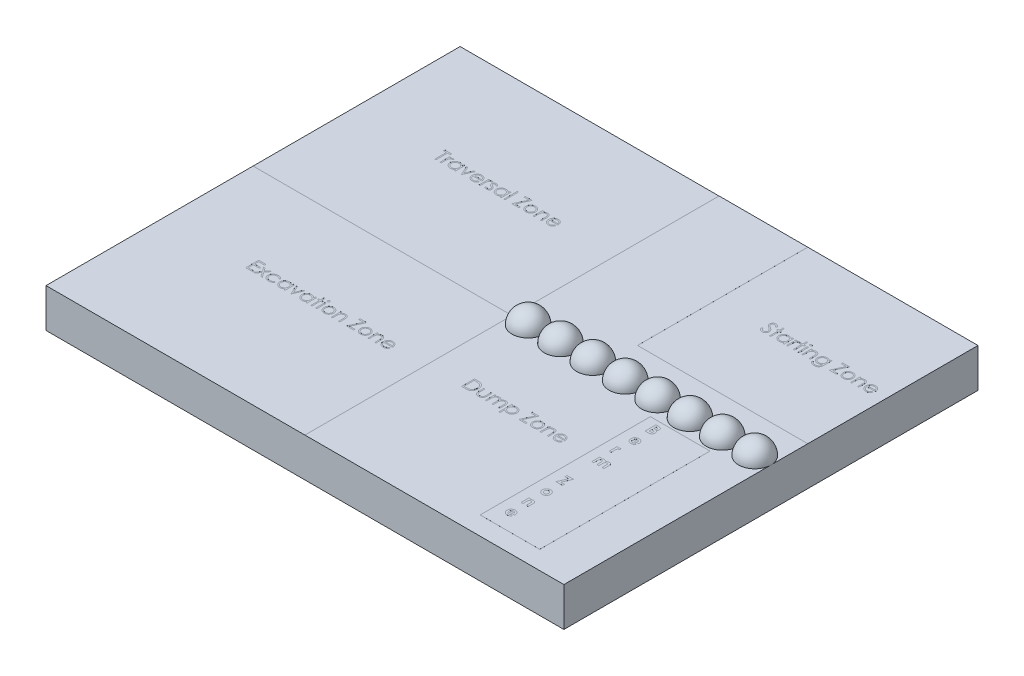
SolidWorks part; units mm, degrees
ref_plane "Front Plane" through (0, 0, 0) normal (0, 0, 1) x (1, 0, 0)
ref_plane "Top Plane" through (0, 0, 0) normal (0, 1, 0) x (1, 0, 0)
ref_plane "Right Plane" through (0, 0, 0) normal (1, 0, 0) x (0, 0, -1)
sketch "Sketch1" plane through (0, 0, 0) normal (0, 1, 0) x (1, 0, 0)
  line L1 (-3042.412, -2432.812) -> (3042.412, -2432.812)
  line L2 (-3042.412, -2432.812) -> (-3042.412, 2432.812)
  line L3 (-3042.412, 2432.812) -> (3042.412, 2432.812)
  line L4 (3042.412, -2432.812) -> (3042.412, 2432.812)
  line L5 (-3042.412, -2432.812) -> (3042.412, 2432.812) construction
  line L6 (-3042.412, 2432.812) -> (3042.412, -2432.812) construction
  point P0 (0, 0)
  dimension "D1" = 4865.624
  dimension "D2" = 6084.824
extrude "Boss-Extrude1" add sketch "Sketch1" along normal blind 457.2
sketch "Sketch2" plane through (0, 457.2, 0) normal (0, 1, 0) x (1, 0, 0)
  line L0 (-3042.412, 0) -> (3042.412, 0)
  line L1 (-3042.412, 2432.812) -> (-3042.412, -2432.812) construction
  line L2 (3042.412, -2432.812) -> (3042.412, 2432.812) construction
  line L3 (0, 2432.812) -> (0, -2432.812)
  line L4 (3042.412, 2432.812) -> (-3042.412, 2432.812) construction
  line L5 (-3042.412, -2432.812) -> (3042.412, -2432.812) construction
  line L7 (-3042.412, -2432.812) -> (3042.412, -2432.812)
  line L8 (-3042.412, -2432.812) -> (-3042.412, 2432.812)
  line L9 (-3042.412, 2432.812) -> (3042.412, 2432.812)
  line L10 (3042.412, -2432.812) -> (3042.412, 2432.812)
  line L11 (-3042.412, -2432.812) -> (3042.412, 2432.812) construction
  line L12 (-3042.412, 2432.812) -> (3042.412, -2432.812) construction
  point P12 (0, 0)
  line M5 (3042.412, -2432.812) -> (3042.412, 2432.812)
  line M6 (3042.412, 2432.812) -> (-3042.412, 2432.812)
  line M7 (-3042.412, 2432.812) -> (-3042.412, -2432.812)
  line M8 (-3042.412, -2432.812) -> (3042.412, -2432.812)
extrude "Cut-Extrude3" cut sketch "Sketch2" against normal blind 0.254 contours L3 L0 M7 M8 region at (-1521.206, 457.2, 1216.406)
extrude "Boss-Extrude2" add sketch "Sketch2<5>" along normal blind 0.254 contours L3 L0 M6 M5 region at (1521.206, 457.2, -1216.406)
sketch "Sketch2<5>" plane through (0, 457.2, 0) normal (0, 1, 0) x (1, 0, 0) same geometry as "Sketch2"
sketch "Sketch4" plane through (0, 457.2, 0) normal (0, 1, 0) x (1, 0, 0)
  line L0 (0, 0) -> (3042.412, 0) construction
  line L1 (0, 0) -> (3042.412, 0) construction
  line L2 (3042.412, 0) -> (3042.412, 2432.812) construction
  line L3 (0, 0) -> (3042.412, 0)
  arc A0 (0, 0) -> (380.3015, 0) centre (190.1508, 0) ccw
  arc A3 (380.3015, 0) -> (760.603, 0) centre (570.4523, 0) ccw
  arc A4 (760.603, 0) -> (1140.9045, 0) centre (950.7538, 0) ccw
  arc A5 (1140.9045, 0) -> (1521.206, 0) centre (1331.0553, 0) ccw
  arc A6 (1521.206, 0) -> (1901.5075, 0) centre (1711.3568, 0) ccw
  arc A7 (1901.5075, 0) -> (2281.809, 0) centre (2091.6582, 0) ccw
  arc A8 (2281.809, 0) -> (2662.1105, 0) centre (2471.9598, 0) ccw
  arc A9 (2662.1105, 0) -> (3042.412, 0) centre (2852.2613, 0) ccw
revolve "Revolve1" add sketch "Sketch4" angle 360 about L3 region at (2852.2613, 457.2, 80.7025) region at (2471.9598, 457.2, 80.7025) region at (2091.6582, 457.2, 80.7025) region at (1711.3568, 457.2, 80.7025) region at (1331.0553, 457.2, 80.7025) region at (950.7538, 457.2, 80.7025) region at (570.4523, 457.2, 80.7025) region at (190.1508, 457.2, 80.7025)
sketch "Sketch6" plane through (0, 457.2, 0) normal (0, 1, 0) x (1, 0, 0)
  text T0 "Traversal Zone" font "Century Gothic" height 152.4
extrude "Cut-Extrude6" cut sketch "Sketch6" against normal blind 0.762
sketch "Sketch7" plane through (0, 456.946, 0) normal (0, 1, 0) x (1, 0, 0)
  text T0 "Excavation Zone" font "Century Gothic" height 152.4
extrude "Cut-Extrude7" cut sketch "Sketch7" against normal blind 0.254
sketch "Sketch8" plane through (0, 457.2, 0) normal (0, 1, 0) x (1, 0, 0)
  text T0 "Dump Zone"
  text T1 "Dump Zone" font "Century Gothic" height 152.4
extrude "Cut-Extrude8" cut sketch "Sketch8" against normal blind 0.254
sketch "Sketch9" plane through (0, 457.2, 0) normal (0, 1, 0) x (1, 0, 0)
  line L1 (-3042.412, 2432.812) -> (0, 2432.812)
  line L2 (-3042.412, 2432.812) -> (-3042.412, 0)
  line L3 (-3042.412, 0) -> (0, 0)
  line L4 (0, 2432.812) -> (0, 0)
extrude "Cut-Extrude9" cut sketch "Sketch9" against normal blind 0.508
sketch "Sketch10" plane through (0, 457.2, 0) normal (0, 1, 0) x (1, 0, 0)
  line L0 (0, -1216.406) -> (3042.412, -1216.406) construction
  line L1 (0, 0) -> (0, -2432.812) construction
  line L2 (3042.412, -2432.812) -> (3042.412, 0) construction
  line L4 (1842.412, -2216.406) -> (2542.412, -2216.406)
  line L5 (1842.412, -2216.406) -> (1842.412, -216.406)
  line L6 (1842.412, -216.406) -> (2542.412, -216.406)
  line L7 (2542.412, -2216.406) -> (2542.412, -216.406)
  line L8 (1842.412, -2216.406) -> (2542.412, -216.406) construction
  line L9 (1842.412, -216.406) -> (2542.412, -2216.406) construction
  point P6 (2192.412, -1216.406)
  dimension "D1" = 700
  dimension "D2" = 2000
  dimension "D3" = 500
extrude "Boss-Extrude3" add sketch "Sketch10" along normal blind 0.254
sketch "Sketch11" plane through (0, 457.454, 0) normal (0, 1, 0) x (1, 0, 0)
  line L0 (1842.412, -216.406) -> (1842.412, -2216.406) construction
  line L1 (2542.412, -216.406) -> (1842.412, -216.406) construction
  text T0 "<b>B</b>\r\n<b>e</b>\r\n<b>r</b>\r\n<b>m</b>\r\n\r\n<b>Z</b>\r\n<b>o</b>\r\n<b>n</b>\r\n<b>e</b>" font "Century Gothic" height 127
  dimension "D1" = 101.6
  dimension "D2" = 177.8
extrude "Boss-Extrude4" add sketch "Sketch11" along normal blind 0.254
sketch "Sketch12" plane through (0, 457.454, 0) normal (0, 1, 0) x (1, 0, 0)
  line L1 (3042.412, 2432.812) -> (1042.412, 2432.812)
  line L2 (3042.412, 2432.812) -> (3042.412, 432.812)
  line L3 (3042.412, 432.812) -> (1042.412, 432.812)
  line L4 (1042.412, 2432.812) -> (1042.412, 432.812)
  dimension "D1" = 2000
extrude "Cut-Extrude10" cut sketch "Sketch12" against normal blind 0.254
sketch "Sketch5" plane through (0, 457.2, 0) normal (0, 1, 0) x (1, 0, 0)
  text T0 "Starting Zone" font "Century Gothic" height 152.4
extrude "Boss-Extrude5" add sketch "Sketch5" along normal blind 0.254
